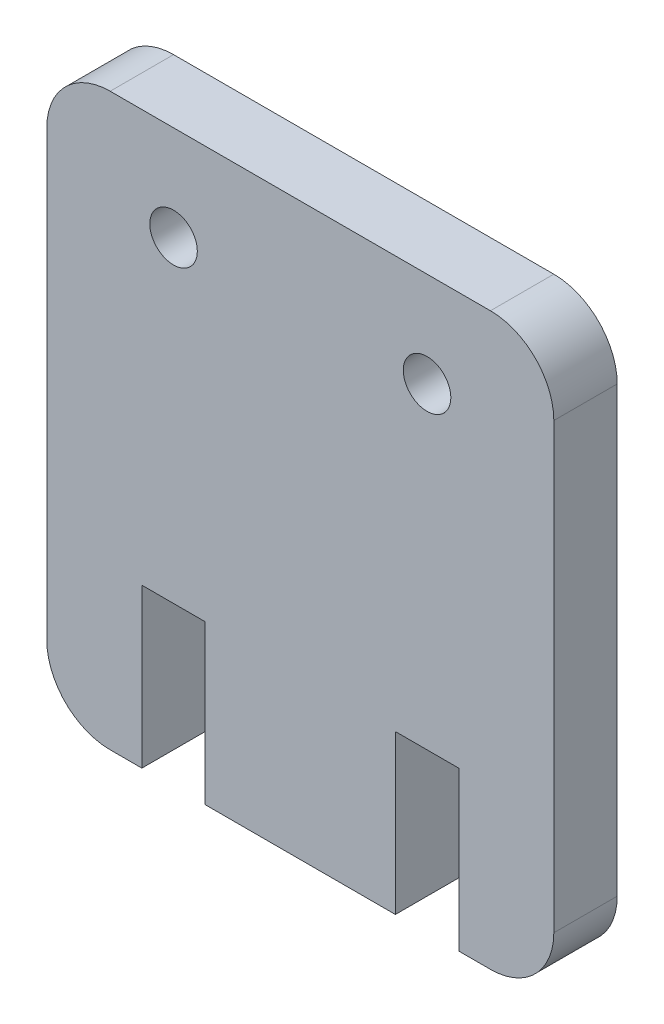
SolidWorks part; units mm, degrees
material "Acrylic (Medium-high impact)"
ref_plane "Front Plane" through (0, 0, 0) normal (0, 0, 1) x (1, 0, 0)
ref_plane "Top Plane" through (0, 0, 0) normal (0, 1, 0) x (1, 0, 0)
ref_plane "Right Plane" through (0, 0, 0) normal (1, 0, 0) x (0, 0, -1)
sketch "Model" plane through (0, 0, 0) normal (0, 0, 1) x (1, 0, 0)
  line L0 (2, 0) -> (3, 0)
  line L1 (3, 0) -> (3, 5)
  line L2 (3, 5) -> (5, 5)
  line L3 (5, 5) -> (5, 0)
  line L4 (5, 0) -> (11, 0)
  line L5 (11, 0) -> (11, 5)
  line L6 (11, 5) -> (13, 5)
  line L7 (13, 5) -> (13, 0)
  line L8 (13, 0) -> (14, 0)
  line L9 (0, 2) -> (0, 16)
  line L10 (2, 18) -> (14, 18)
  line L11 (16, 16) -> (16, 2)
  circle A0 centre (4, 15) radius 0.75
  circle A3 centre (12, 15) radius 0.75
  arc A4 (0, 16) -> (2, 18) centre (2, 16) cw
  arc A5 (2, 0) -> (0, 2) centre (2, 2) cw
  arc A6 (16, 2) -> (14, 0) centre (14, 2) cw
  arc A7 (14, 18) -> (16, 16) centre (14, 16) cw
  point P13 (0, 0)
  dimension "D1" = 1.5
  dimension "D2" = 2
  dimension "D3" = 16
  dimension "D4" = 13
  dimension "D7" = 3
  dimension "D5" = 6
  dimension "D6" = 2
  dimension "D8" = 4
  dimension "D9" = 4
  dimension "D10" = 5
other "AlignGroup1"
other "AlignGroup2"
other "AlignGroup3"
other "AlignGroup4"
other "AlignGroup5"
other "AlignGroup6"
other "AlignGroup7"
other "AlignGroup8"
extrude "Boss-Extrude1" add sketch "Model" along normal blind 2
